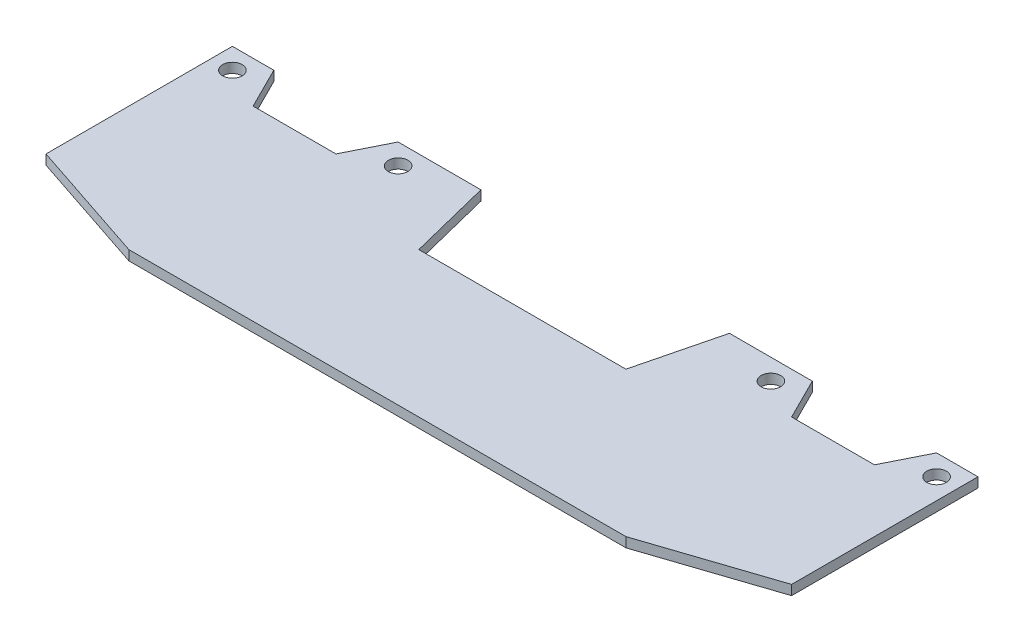
SolidWorks part; units mm, degrees
material "Ti-6Al-4VSolution treated and aged (SS)"
ref_plane "Front Plane" through (0, 0, 0) normal (0, 0, 1) x (1, 0, 0)
ref_plane "Top Plane" through (0, 0, 0) normal (0, 1, 0) x (1, 0, 0)
ref_plane "Right Plane" through (0, 0, 0) normal (1, 0, 0) x (0, 0, -1)
sketch "Sketch1" plane through (0, 0, 0) normal (0, 1, 0) x (1, 0, 0)
  line L0 (-57.15, -11.1125) -> (-38.1, -17.4625)
  line L1 (-38.1, -17.4625) -> (38.1, -17.4625)
  line L2 (-57.15, -11.1125) -> (-57.15, 17.4625)
  line L3 (-57.15, 17.4625) -> (-19.05, 17.4625)
  line L4 (57.15, -11.1125) -> (57.15, 17.4625)
  line L5 (-57.15, -17.4625) -> (57.15, 17.4625) construction
  line L6 (-57.15, 17.4625) -> (57.15, -17.4625) construction
  line L7 (0, 17.4625) -> (0, -17.4625) construction
  line L8 (57.15, -11.1125) -> (38.1, -17.4625)
  line L9 (-57.15, -17.4625) -> (-57.15, -11.1125) construction
  line L10 (-57.15, -17.4625) -> (-38.1, -17.4625) construction
  line L11 (38.1, -17.4625) -> (57.15, -17.4625) construction
  line L12 (57.15, -17.4625) -> (57.15, -11.1125) construction
  line L13 (-19.05, 17.4625) -> (-15.875, 4.7625)
  line L14 (-15.875, 4.7625) -> (15.875, 4.7625)
  line L15 (19.05, 17.4625) -> (15.875, 4.7625)
  line L16 (19.05, 17.4625) -> (57.15, 17.4625)
  line L17 (-19.05, 17.4625) -> (0, 17.4625) construction
  line L18 (0, 17.4625) -> (19.05, 17.4625) construction
  point P0 (0, 0)
  point P16 (0, 4.7625)
  dimension "D1" = 114.3
  dimension "D2" = 34.925
  dimension "D3" = 19.05
  dimension "D4" = 6.35
  dimension "D5" = 38.1
  dimension "D6" = 31.75
  dimension "D7" = 12.7
extrude "Boss-Extrude1" add sketch "Sketch1" along normal blind 1.4985
sketch "Sketch2" plane through (0, 1.4985, 0) normal (0, 1, 0) x (1, 0, 0)
  line L0 (-53.975, 14.2875) -> (-28.575, 14.2875) construction
  line L1 (-19.05, 17.4625) -> (-57.15, 17.4625) construction
  line L3 (-57.15, 17.4625) -> (-57.15, -11.1125) construction
  circle A0 centre (-53.975, 14.2875) radius 1.5
  circle A4 centre (-28.575, 14.2875) radius 1.5
  dimension "D1" = 3
  dimension "D2" = 3.175
  dimension "D3" = 3.175
  dimension "D4" = 25.4
extrude "Cut-Extrude1" cut sketch "Sketch2" against normal through all
sketch "Sketch5" plane through (0, 1.4985, 0) normal (0, 1, 0) x (1, 0, 0)
  line L0 (-50.8, 17.4625) -> (-47.625, 11.1125)
  line L1 (-19.05, 17.4625) -> (-57.15, 17.4625) construction
  line L2 (-47.625, 11.1125) -> (-34.925, 11.1125)
  line L3 (-34.925, 11.1125) -> (-31.75, 17.4625)
  line L4 (-53.975, 14.2875) -> (-50.8, 17.4625) construction
  line L5 (-28.575, 14.2875) -> (-31.75, 17.4625) construction
  line L6 (-50.8, 17.4625) -> (-31.75, 17.4625)
  dimension "D1" = 6.35
  dimension "D2" = 3.175
  dimension "D3" = 3.175
extrude "Cut-Extrude2" cut sketch "Sketch5" against normal through all
mirror "Mirror1" about plane through (0, 0, 0) normal (1, 0, 0) of "Cut-Extrude2", "Cut-Extrude1"
